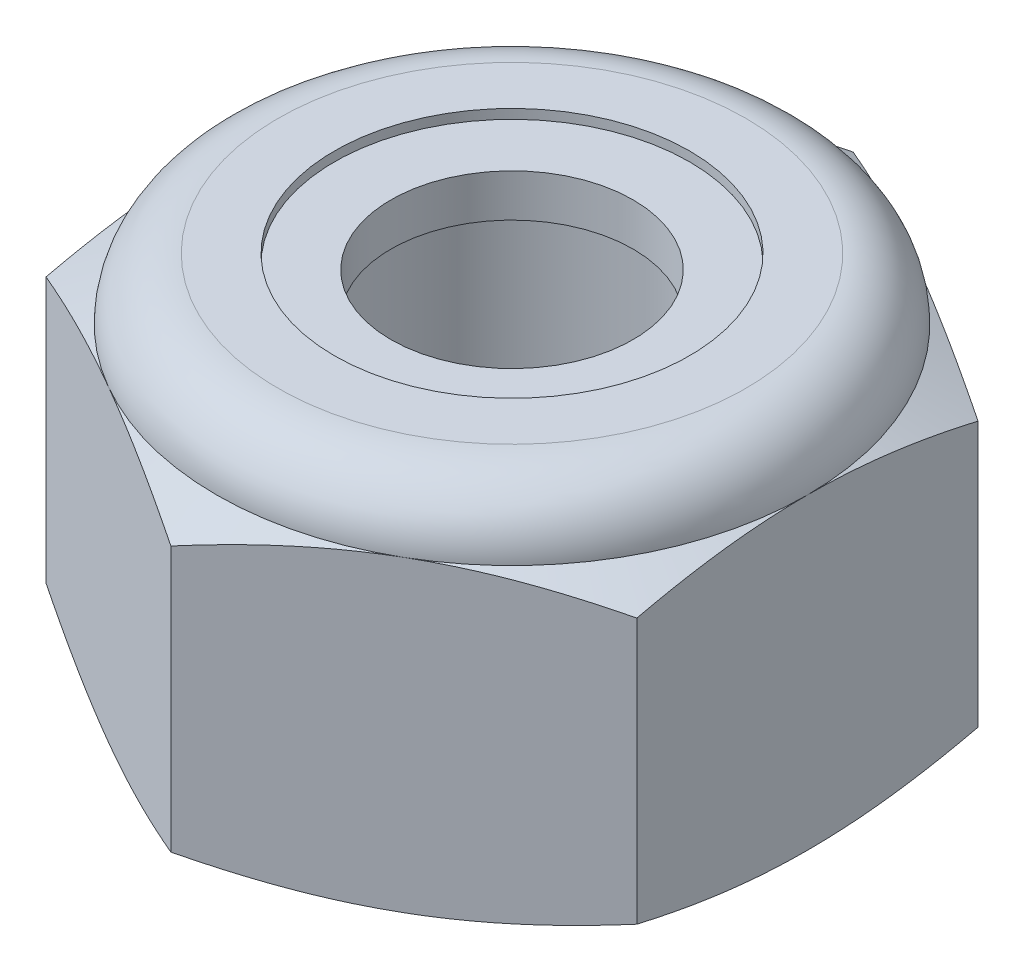
SolidWorks part; units mm, degrees
ref_plane "Front" through (0, 0, 0) normal (0, 0, 1) x (1, 0, 0)
ref_plane "Top" through (0, 0, 0) normal (0, 1, 0) x (1, 0, 0)
ref_plane "Right" through (0, 0, 0) normal (1, 0, 0) x (0, 0, -1)
sketch "Sketch1" plane through (0, 0, 0) normal (0, 1, 0) x (1, 0, 0)
  line L1 (0, 5.4993) -> (-4.7625, 2.7496)
  line L2 (-4.7625, 2.7496) -> (-4.7625, -2.7496)
  line L3 (-4.7625, -2.7496) -> (0, -5.4993)
  line L4 (0, -5.4993) -> (4.7625, -2.7496)
  line L5 (4.7625, -2.7496) -> (4.7625, 2.7496)
  line L6 (4.7625, 2.7496) -> (0, 5.4993)
  circle A0 centre (0, 0) radius 4.7625 construction
  dimension "Hex Flats" = 9.525
extrude "Extrude1" add sketch "Sketch1" along normal blind 5.9531
sketch "Sketch2" plane through (0, 0, 0) normal (1, 0, 0) x (0, 0, -1)
  line L0 (-2.413, 0) -> (-2.413, 5.9531) construction
  line L1 (0, 0) -> (2.413, 0)
  line L2 (0, 0) -> (0, 5.9531)
  line L3 (0, 5.9531) -> (2.413, 5.9531)
  line L4 (2.413, 0) -> (2.413, 5.9531)
  line L5 (-2.7496, 5.9531) -> (2.7496, 5.9531) construction
  line L7 (0, -2.413) -> (0, 0) construction
  dimension "Thread Dia" = 4.826
revolve "Revolve1" add sketch "Sketch2" angle 360 about L7
sketch "Sketch3" plane through (0, 0, 0) normal (1, 0, 0) x (0, 0, -1)
  line L0 (2.413, 5.9531) -> (-2.413, 5.9531) construction
  line L1 (-2.413, 5.9531) -> (-2.413, 4.8948) construction
  line L2 (-2.413, 4.8948) -> (2.413, 5.9531) construction
  line L3 (2.413, 5.9531) -> (2.4413, 5.8239) construction
  line L4 (2.4413, 5.8239) -> (2.6397, 4.9194)
  line L5 (2.6397, 4.9194) -> (2.0093, 5.1197)
  line L6 (2.0093, 5.1197) -> (1.9526, 5.3781)
  line L7 (1.9526, 5.3781) -> (2.4413, 5.8239)
  line L8 (1.981, 5.2489) -> (2.5405, 5.3716) construction
  line L9 (2.413, 5.9531) -> (2.413, 5.3437) construction
  line L10 (2.413, 5.3437) -> (-2.413, 4.2853) construction
  line L11 (-2.413, 4.2853) -> (-2.413, 4.8948) construction
  line L12 (-0.2497, 5.9531) -> (0.2497, 3.6759) construction
  line L13 (-2.413, 0) -> (-2.413, 5.9531) construction
  line L14 (0, 5.9531) -> (2.413, 5.9531) construction
  line L15 (2.413, 0) -> (2.413, 5.9531) construction
  point P13 (0, 4.8145)
  dimension "D1" = 0.1323
  dimension "D2" = 0.2646
  dimension "Thread Pitch" = 1.0583
  dimension "D4" = 60
  dimension "D5" = 1.0583
revolve "Cut-Revolve1" [suppressed] cut sketch "Sketch3" angle 360 about L12
pattern_linear "LPattern1" [suppressed] count 6 spacing 1.0583 along (0, -1, 0) count 2 spacing 1.0583 along (0, 1, 0) of bodies 110
sketch "Sketch4" plane through (0, 0, 0) normal (1, 0, 0) x (0, 0, -1)
  line L0 (0, 5.9531) -> (2.413, 5.9531)
  line L1 (2.413, 5.9531) -> (1.9526, 5.7385)
  line L2 (1.9526, 5.7385) -> (1.9526, 0.2147)
  line L3 (1.9526, 0.2147) -> (2.413, 0)
  line L4 (2.413, 0) -> (0, 0)
  line L5 (0, 0) -> (0, 5.9531)
  line L6 (2.413, 0) -> (2.413, 5.9531) construction
  line L7 (0, 5.9531) -> (2.413, 5.9531) construction
  line L8 (0, 0) -> (2.413, 0) construction
  line L9 (0, 0) -> (0, 5.9531) construction
  line L10 (0, 5.9531) -> (0, 6.4611) construction
  dimension "D1" = 25
revolve "Cut-Revolve2" cut sketch "Sketch4" angle 360 about L10
combine bodies "Combine1" operation type subtract main body 112 bodies to subtract 109
sketch "Sketch5" plane through (0, 0, 0) normal (1, 0, 0) x (0, 0, -1)
  line L0 (0, 0) -> (4.7625, 0)
  line L1 (4.7625, 0) -> (5.4993, 0.3436)
  line L2 (5.4993, 0.3436) -> (5.4993, 4.6174)
  line L3 (5.4993, 4.6174) -> (4.7625, 4.9609)
  line L4 (3.7703, 5.9531) -> (3.7703, 7.2231)
  line L5 (3.7703, 7.2231) -> (6.7693, 7.2231)
  line L6 (6.7693, 7.2231) -> (6.7693, -1.27)
  line L7 (6.7693, -1.27) -> (0, -1.27)
  line L8 (0, -1.27) -> (0, 0)
  line L9 (4.7625, 4.9609) -> (4.7625, 0) construction
  line L10 (0, 0) -> (2.413, 0) construction
  line L13 (5.4993, 2.4805) -> (6.7693, 2.4805) construction
  line L14 (5.4993, 5.9531) -> (5.4993, 0) construction
  line L15 (0, 0) -> (0, 7.2231) construction
  line L20 (0, 7.2231) -> (3.7703, 7.2231) construction
  line L22 (0, 5.9531) -> (2.413, 5.9531) construction
  arc A0 (4.7625, 4.9609) -> (3.7703, 5.9531) centre (3.7703, 4.9609) ccw
  dimension "D1" = 25
  dimension "D2" = 1.27
  dimension "D3" = 5.9531
  dimension "D4" = 0.9922
revolve "Cut-Revolve3" cut sketch "Sketch5" angle 360 about L15
sketch "Sketch6" plane through (0, 0, 0) normal (1, 0, 0) x (0, 0, -1)
  line L0 (0, 4.9609) -> (4.6101, 4.9609)
  line L1 (3.7703, 5.8007) -> (2.8615, 5.8007)
  line L2 (0, 7.2231) -> (0, 4.9609)
  line L3 (2.8615, 7.2231) -> (0, 7.2231)
  line L4 (0, 7.2231) -> (3.7703, 7.2231) construction
  line L5 (0, 0) -> (0, 7.2231) construction
  line L6 (0, 7.2231) -> (0, 44.323) construction
  line L7 (2.8615, 5.8007) -> (2.8615, 7.2231)
  line L8 (3.7703, 5.9531) -> (3.7703, 5.8007) construction
  line L9 (2.8615, 5.8007) -> (1.9526, 5.8007) construction
  line L10 (1.9526, 5.8007) -> (1.9526, 5.7385) construction
  arc A0 (4.6101, 4.9609) -> (3.7703, 5.8007) centre (3.7703, 4.9609) ccw
  arc A1 (4.7625, 4.9609) -> (3.7703, 5.9531) centre (3.7703, 4.9609) ccw construction
  dimension "D1" = 0.1524
revolve "Cut-Revolve4" cut sketch "Sketch6" angle 360 about L6
sketch "Sketch7" plane through (0, 0, 0) normal (1, 0, 0) x (0, 0, -1)
  line L0 (1.9526, 5.0371) -> (4.5301, 5.0371)
  line L1 (3.7703, 5.7245) -> (1.9526, 5.7245)
  line L2 (1.9526, 5.7245) -> (1.9526, 5.0371)
  line L3 (1.9526, 5.0371) -> (0, 5.0371) construction
  line L4 (0, 5.0371) -> (0, 5.7245) construction
  line L5 (0, 5.7245) -> (1.9526, 5.7245) construction
  line L6 (1.9526, 5.0371) -> (1.9526, 4.9609) construction
  line L7 (0, 4.9609) -> (4.6101, 4.9609) construction
  line L8 (3.7703, 5.7245) -> (3.7703, 5.8007) construction
  arc A0 (4.5301, 5.0371) -> (3.7703, 5.7245) centre (3.7703, 4.9609) ccw
  arc A2 (4.6101, 4.9609) -> (3.7703, 5.8007) centre (3.7703, 4.9609) ccw construction
  dimension "D1" = 0.0762
revolve "Revolve2" add sketch "Sketch7" angle 360 about L4
equation "\"D1@Sketch3\"=\"Thread Pitch@Sketch3\"/8"
equation "\"D2@Sketch3\"=\"Thread Pitch@Sketch3\"/4"
equation "\"D5@Sketch3\"=\"Thread Pitch@Sketch3\""
equation "\"D4@LPattern1\"=\"Thread Pitch@Sketch3\""
equation "\"D3@LPattern1\"=\"Thread Pitch@Sketch3\""
equation "\"D1@LPattern1\"=\"Height@Extrude1\"/\"Thread Pitch@Sketch3\""
equation "\"D4@Sketch5\"=\"Height@Extrude1\"/6"
